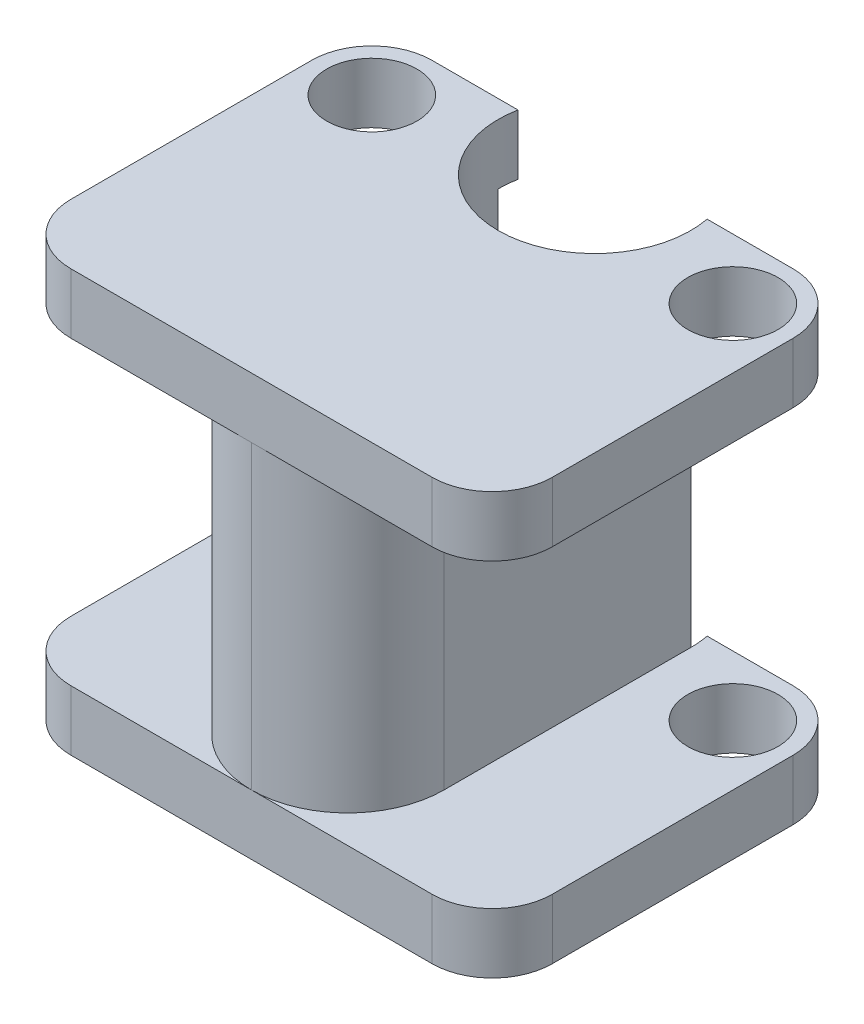
SolidWorks part; units mm, degrees
ref_plane "Front Plane" through (0, 0, 0) normal (0, 0, 1) x (1, 0, 0)
ref_plane "Top Plane" through (0, 0, 0) normal (0, 1, 0) x (1, 0, 0)
ref_plane "Right Plane" through (0, 0, 0) normal (1, 0, 0) x (0, 0, -1)
sketch "Sketch1" plane through (0, 0, 0) normal (0, 1, 0) x (1, 0, 0)
  line L0 (-3.2, 7.4) -> (-3.2, 4)
  line L1 (-3.2, -4) -> (3.2, -4)
  line L2 (-3.2, -4) -> (-3.2, 4)
  line L4 (3.2, -4) -> (3.2, 4)
  line L5 (0, 4.2) -> (0, -4) construction
  line L6 (-3.2, 0) -> (3.2, 0) construction
  line L7 (3.2, 7.4) -> (3.2, 4)
  line L8 (-3.2, 7.4) -> (3.2, 7.4) construction
  line L9 (-3.2, 4) -> (3.2, 4) construction
  arc A0 (-3.2, 7.4) -> (3.2, 7.4) centre (0, 7.4) ccw
  point P0 (0, 0)
  point P7 (0, 4.2)
  point P8 (0, 4.3441)
  dimension "D1" = 6.4
  dimension "D2" = 8
  dimension "D3" = 3.4
  dimension "D4" = 8.2
extrude "Boss-Extrude1" add sketch "Sketch1" along normal blind 10
sketch "Sketch2" plane through (0, 10, 0) normal (0, 1, 0) x (1, 0, 0)
  line L5 (-3.2, -4) -> (3.2, -4) construction
  line L6 (-8, 8) -> (-3.1432, 8)
  line L8 (-8, 8) -> (-8, -4)
  line L9 (-8, -4) -> (8, -4)
  line L10 (8, 8) -> (8, -4)
  line L11 (0, -4) -> (0, 4.2) construction
  line L12 (-8, 2) -> (8, 2) construction
  line L13 (3.1432, 8) -> (8, 8)
  arc A3 (-3.1432, 8) -> (3.1432, 8) centre (0, 7.4) ccw
  arc A4 (-3.2, 7.4) -> (3.2, 7.4) centre (0, 7.4) ccw construction
  point P12 (0, 4.2)
  point P189 (0, 2)
  dimension "D1" = 16
  dimension "D2" = 12
extrude "Boss-Extrude2" add sketch "Sketch2" along normal blind 2
sketch "Sketch3" plane through (0, 0, 0) normal (0, -1, 0) x (1, 0, 0)
  line L0 (8, 4) -> (-8, 4)
  line L1 (-8, 4) -> (-8, -8)
  line L2 (-8, -8) -> (-3.1432, -8)
  line L3 (8, 4) -> (8, -8)
  line L4 (8, -8) -> (3.1432, -8)
  arc A0 (-3.1432, -8) -> (3.1432, -8) centre (0, -7.4) cw
  arc A1 (3.2, -7.4) -> (-3.2, -7.4) centre (0, -7.4) ccw construction
  point P3 (-8, -8)
  point P4 (-3.3834, -8)
  point P6 (0, -6.714)
  point P13 (-3.3834, -8)
  point P15 (0, 0)
  point P19 (3.3834, -8)
fillet "Fillet1" radius 3.2 2 edges at (-3.2, 5, 4) (3.2, 5, 4)
extrude "Boss-Extrude4" add sketch "Sketch3" along normal blind 2
fillet "Fillet3" radius 2 8 edges at (8, 11, -8) (8, 11, 4) (8, -1, -8) (8, -1, 4) (-8, -1, -8) (-8, 11, -8) (-8, 11, 4) (-8, -1, 4)
sketch "Sketch5" plane through (0, 12, 0) normal (0, 1, 0) x (1, 0, 0)
  circle A0 centre (-6, 6) radius 1.5
  circle A1 centre (6, 6) radius 1.5
  arc A2 (-6, 8) -> (-8, 6) centre (-6, 6) ccw construction
  arc A3 (8, 6) -> (6, 8) centre (6, 6) ccw construction
  point P7 (0, 0)
  point P8 (0, 0)
  dimension "D1" = 3
  dimension "D2" = 3
extrude "Cut-Extrude1" cut sketch "Sketch5" against normal blind 14
